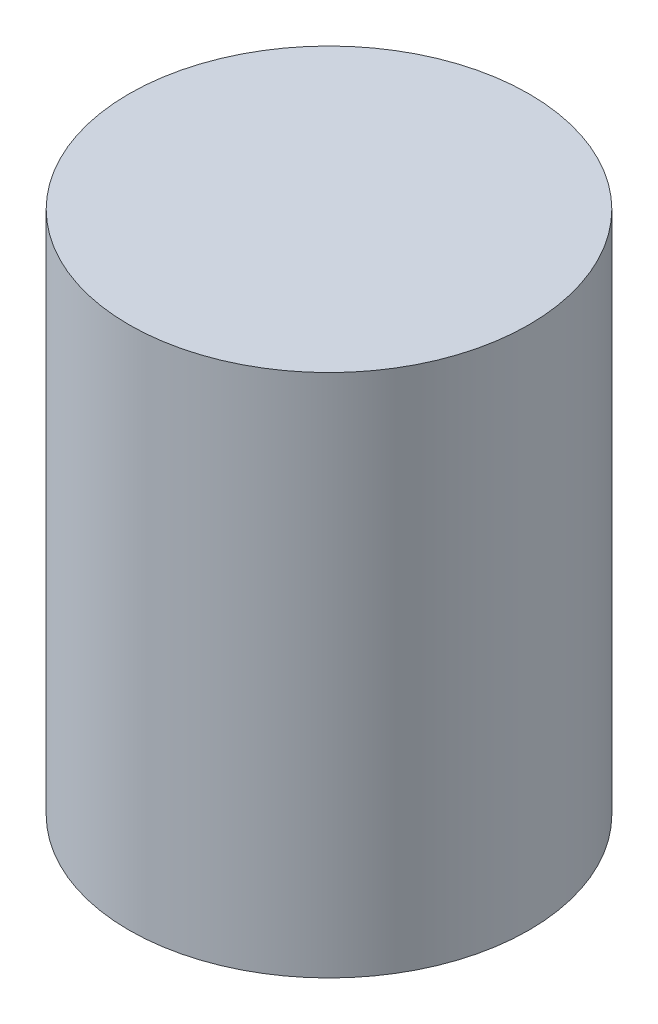
SolidWorks part; units mm, degrees
material "1060-O (SS)"
ref_plane "Front Plane" through (0, 0, 0) normal (0, 0, 1) x (1, 0, 0)
ref_plane "Top Plane" through (0, 0, 0) normal (0, 1, 0) x (1, 0, 0)
ref_plane "Right Plane" through (0, 0, 0) normal (1, 0, 0) x (0, 0, -1)
sketch "Sketch1" plane through (0, 0, 0) normal (0, 1, 0) x (1, 0, 0)
  circle A0 centre (0, 0) radius 24.9
  point P3 (0, 0)
  point P4 (0, 0)
  dimension "D1" = 49.8
extrude "Boss-Extrude1" add sketch "Sketch1" along normal blind 65.278 contours A0
